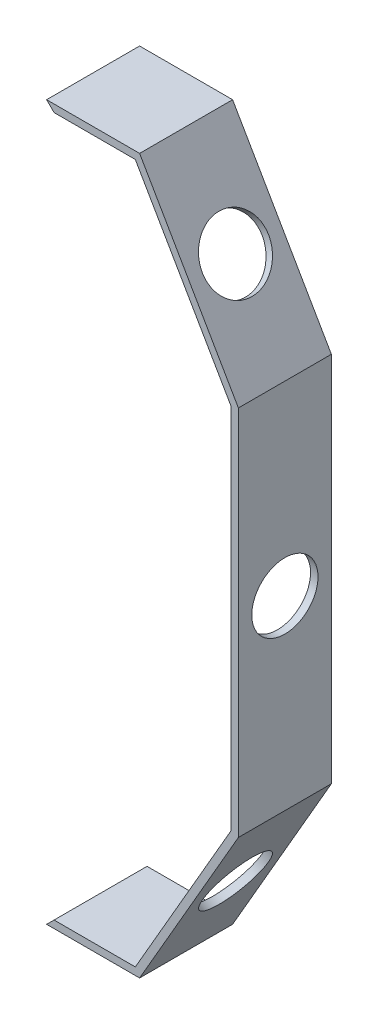
SolidWorks part; units mm, degrees
ref_plane "Alzado" through (0, 0, 0) normal (0, 0, 1) x (1, 0, 0)
ref_plane "Planta" through (0, 0, 0) normal (0, 1, 0) x (1, 0, 0)
ref_plane "Vista lateral" through (0, 0, 0) normal (1, 0, 0) x (0, 0, -1)
sketch "Croquis1" plane through (0, 0, 0) normal (0, 0, 1) x (1, 0, 0)
  line L20 (12.5, 96) -> (39.0581, 50)
  line L21 (-12.5, -96) -> (12.5, -96)
  line L23 (-12.5, 96) -> (12.5, 96)
  line L24 (39.0581, -50) -> (39.0581, 50)
  line L25 (39.0581, -50) -> (12.5, -96)
  line L26 (11.3453, 94) -> (37.0581, 49.4641)
  line L27 (37.0581, -49.4641) -> (37.0581, 49.4641)
  line L28 (37.0581, -49.4641) -> (11.3453, -94)
  line L29 (-10.5, -94) -> (11.3453, -94)
  line L31 (-10.5, 94) -> (11.3453, 94)
  line L32 (-12.5, 96) -> (-10.5, 94)
  line L33 (-10.5, -94) -> (-12.5, -96)
  line L35 (-12.5, -96) -> (-12.5, 96) construction
  line L36 (-10.5, -94) -> (-10.5, 94) construction
  point P2 (39.0581, 0)
  point P13 (0, 0)
  point P14 (0, 0)
  point P15 (0, 0)
  point P17 (0, 0)
  point P18 (0, 96)
  point P19 (0, -96)
  dimension "D1" = 100
  dimension "D3" = 60
  dimension "D4" = 2
  dimension "D5" = 192
  dimension "D6" = 25
extrude "Saliente-Extruir2" add sketch "Croquis1" along normal blind 25
sketch "Croquis3" plane through (39.0581, 0, 0) normal (1, 0, 0) x (0, 0, -1)
  line L0 (-25, 50) -> (0, 50) construction
  circle A0 centre (-12.5, 0) radius 8.9
  point P2 (0, 0)
  point P6 (-12.5, 50)
  dimension "D1" = 17.8
extrude "Cortar-Extruir1" cut sketch "Croquis3" against normal blind 25
sketch "Croquis4" plane through (50.9442, 29.4127, 0) normal (0.866, 0.5, 0) x (0, 0, -1)
  line L0 (-25, 76.8884) -> (0, 76.8884) construction
  line L1 (0, 23.7722) -> (0, 76.8884) construction
  circle A0 centre (-12.5, 50.3303) radius 8.9
  point P2 (0, 0)
  point P5 (-12.5, 76.8884)
  point P8 (0, 50.3303)
  dimension "D1" = 17.8
extrude "Cortar-Extruir2" cut sketch "Croquis4" against normal blind 25
sketch "Croquis5" plane through (50.9442, -29.4127, 0) normal (0.866, -0.5, 0) x (0, 0, -1)
  line L0 (-25, -23.7722) -> (0, -23.7722) construction
  line L1 (0, -76.8884) -> (0, -23.7722) construction
  circle A0 centre (-12.5, -50.3303) radius 8.9
  point P4 (-12.5, -23.7722)
  point P7 (0, -50.3303)
  dimension "D1" = 17.8
extrude "Cortar-Extruir3" cut sketch "Croquis5" against normal blind 25
